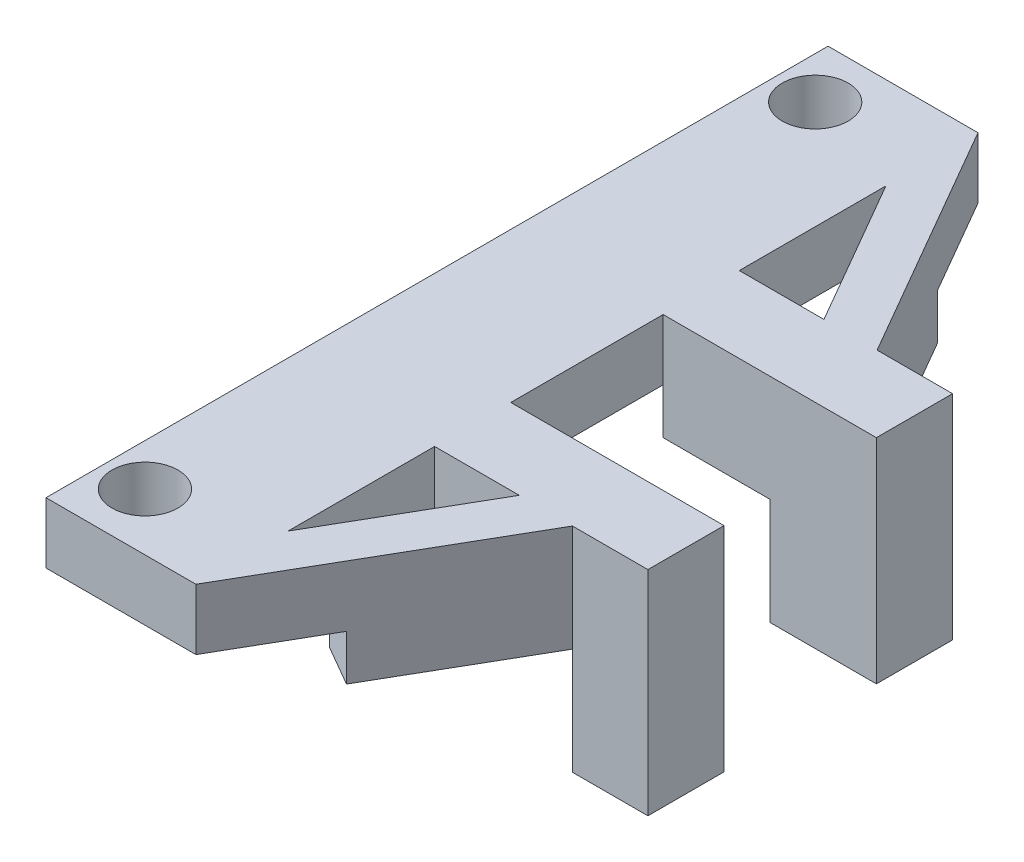
SolidWorks part; units mm, degrees
ref_plane "Front Plane" through (0, 0, 0) normal (0, 0, 1) x (1, 0, 0)
ref_plane "Top Plane" through (0, 0, 0) normal (0, 1, 0) x (1, 0, 0)
ref_plane "Right Plane" through (0, 0, 0) normal (1, 0, 0) x (0, 0, -1)
sketch "Sketch1" plane through (0, 0, 0) normal (0, 1, 0) x (1, 0, 0)
  line L0 (4.5, 30.226) -> (10.6074, 19.6478)
  line L1 (0, 2.375) -> (4.5, 2.375)
  line L2 (0, 2.375) -> (0, -2.375)
  line L3 (0, -2.375) -> (4.5, -2.375)
  line L4 (4.5, 2.375) -> (4.5, -2.375)
  line L5 (0, 2.375) -> (-1.75, 2.375)
  line L6 (0, 2.375) -> (0, -2.375)
  line L7 (0, -2.375) -> (-1.75, -2.375)
  line L8 (-1.75, 2.375) -> (-1.75, -2.375)
  line L9 (-1.75, 2.375) -> (4.5, 2.375)
  line L10 (-1.75, 2.375) -> (-1.75, 30.226)
  line L11 (-1.75, 30.226) -> (4.5, 30.226)
  line L12 (4.5, 2.375) -> (4.5, 30.226)
  line L13 (4.5, 30.226) -> (2.8376, 29.2662)
  line L14 (10.6074, 19.6478) -> (8.945, 18.688)
  line L15 (2.8376, 29.2662) -> (8.945, 18.688)
  line L20 (4.5, -2.375) -> (10.6074, 8.2032)
  line L21 (4.5, -2.375) -> (2.8376, -1.4152)
  line L22 (10.6074, 8.2032) -> (8.945, 9.163)
  line L23 (2.8376, -1.4152) -> (8.945, 9.163)
  line L24 (5.135, 2.5639) -> (6.7974, 1.6041)
  line L25 (4.5, 7.5755) -> (13.39, 7.5755)
  line L26 (4.5, 7.5755) -> (4.5, 10.7505)
  line L27 (4.5, 10.7505) -> (13.39, 10.7505)
  line L28 (13.39, 7.5755) -> (13.39, 10.7505)
  line L29 (4.5, 7.5755) -> (13.39, 10.7505) construction
  line L30 (4.5, 10.7505) -> (13.39, 7.5755) construction
  line L31 (4.5, 17.1005) -> (13.39, 17.1005)
  line L32 (4.5, 17.1005) -> (4.5, 20.2755)
  line L33 (4.5, 20.2755) -> (13.39, 20.2755)
  line L34 (13.39, 17.1005) -> (13.39, 20.2755)
  line L35 (4.5, 17.1005) -> (13.39, 20.2755) construction
  line L36 (4.5, 20.2755) -> (13.39, 17.1005) construction
  line L37 (0, 2.375) -> (0, 30.226) construction
  line L38 (5.135, 25.2871) -> (7.6421, 26.7346)
  line L39 (8.945, 20.2755) -> (8.945, 17.1005)
  line L40 (8.945, 10.7505) -> (8.945, 7.5755)
  circle A0 centre (0, 0) radius 1.375
  circle A1 centre (0, 27.94) radius 1.375
  point P7 (0, 0)
  dimension "D1" = 2.75
  dimension "D6" = 2.75
  dimension "D11" = 1.75
  dimension "D2" = 1.75
  dimension "D3" = 4.75
  dimension "D4" = 6.25
  dimension "D5" = 2.286
  dimension "D7" = 27.94
  dimension "D8" = 60
  dimension "D9" = 60
  dimension "D10" = 6.35
  dimension "D12" = 3.175
  dimension "D13" = 8.89
  dimension "D14" = 7.62
  dimension "D15" = 7.62
extrude "Boss-Extrude1" add sketch "Sketch1" along normal blind 2.54 contours A0 L2 L5 L8 L7 | A0 L2 L3 L4 L1 | L15 L13 L11 L10 L5 L1 L12 | L15 L0 L12 | L15 L14 | L13 L15 L12 | L25 L23 L12 L4 L20 | L23 L21 L4 L9 | L23 L9 L12 | L23 L25 L20 L22 | L25 L28 L27 L26 L23 L22 L20 | L33 L32 L31 L12 | L40 L27 L12 L25 L23 | L32 L33 L34 L31 | L20 L21 L23 L22 | L0 L13 L15 L14 region at (1.3748, 0, -15.6429) region at (5.3116, 0, -27.2634) region at (3.9459, 0, -28.6264) region at (-0.875, 0, -2.3244) region at (6.6183, 0, -18.6305) region at (8.6395, 0, -19.7463) region at (2.2196, 0, -0.1626) region at (6.6183, 0, -9.2205) region at (3.9459, 0, 0.7754) region at (11.3859, 0, -9.2989) region at (7.5797, 0, -4.8228) region at (9.6015, 0, -8.1889)
extrude "Boss-Extrude3" add sketch "Sketch1<3>" against normal blind 1.905 contours L27 L40 L22 L20 L25 L28 | L40 L27 L12 L25 L23 | L25 L23 L24 L20 | L22 L40 L25 L20 | L40 L23 L25 | L14 L39 L31 L34 L33 L0 | L39 L15 L33 L12 L31 | L39 L33 L15 | L33 L39 L14 L0 | L38 L15 L33 L0 region at (7.5797, 0, -23.0282) region at (11.3859, 0, -18.5521) region at (9.6015, 0, -19.6621) region at (6.6183, 0, -18.6305) region at (8.6395, 0, -19.7463) region at (6.6183, 0, -9.2205) region at (11.3859, 0, -9.2989) region at (7.5797, 0, -4.8228) region at (8.6395, 0, -8.1047) region at (9.6015, 0, -8.1889)
sketch "Sketch1<3>" plane through (0, 0, 0) normal (0, 1, 0) x (1, 0, 0) same geometry as "Sketch1"
extrude "Boss-Extrude4" add sketch "Sketch1<4>" against normal blind 6.35 contours L25 L28 L27 L12 L23 L22 L20 | L31 L34 L33 L0 L14 L15 L12 region at (11.3859, 0, -18.5521) region at (11.3859, 0, -9.2989)
sketch "Sketch1<4>" plane through (0, 0, 0) normal (0, 1, 0) x (1, 0, 0) same geometry as "Sketch1"
